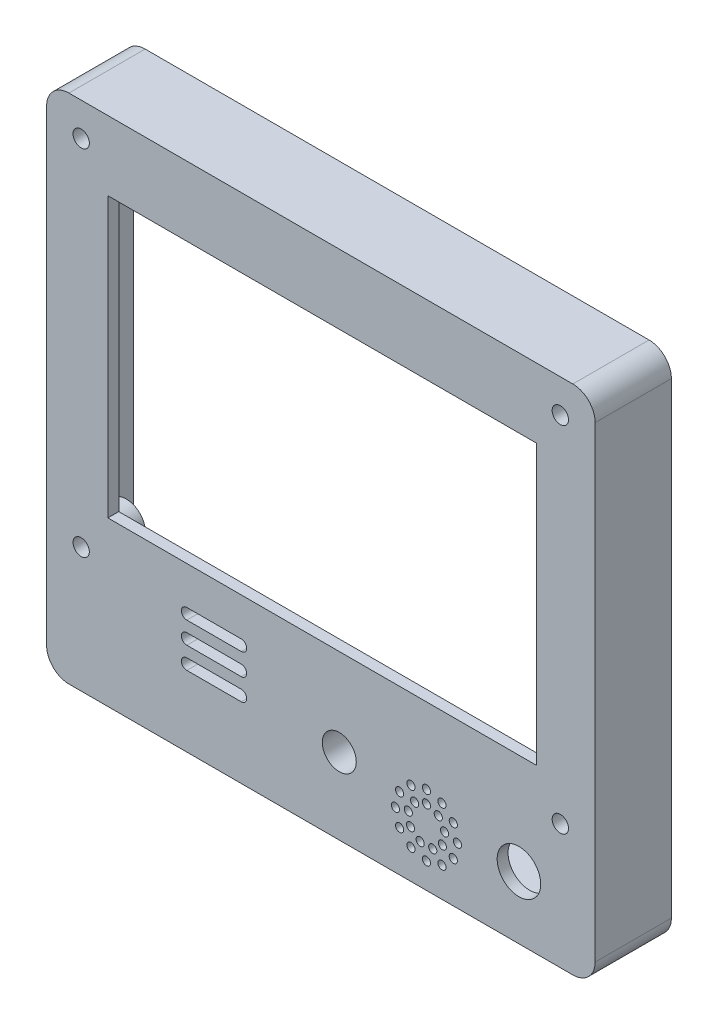
SolidWorks part; units mm, degrees
ref_plane "Front Plane" through (0, 0, 0) normal (0, 0, 1) x (1, 0, 0)
ref_plane "Top Plane" through (0, 0, 0) normal (0, 1, 0) x (1, 0, 0)
ref_plane "Right Plane" through (0, 0, 0) normal (1, 0, 0) x (0, 0, -1)
sketch "Sketch1" plane through (0, 0, 0) normal (0, 0, 1) x (1, 0, 0)
  line L1 (-50.375, -47) -> (50.375, -47)
  line L2 (-50.375, -47) -> (-50.375, 47)
  line L3 (-50.375, 47) -> (50.375, 47)
  line L4 (50.375, -47) -> (50.375, 47)
  line L5 (-50.375, -47) -> (50.375, 47) construction
  line L6 (-50.375, 47) -> (50.375, -47) construction
  point P0 (0, 0)
  dimension "D1" = 100.75
  dimension "D2" = 94
extrude "Boss-Extrude1" add sketch "Sketch1" along normal blind 14
shell "Shell1" thickness 2 removed face at (0, 0, 0)
sketch "Sketch2" plane through (0, 0, 12) normal (0, 0, -1) x (-1, 0, 0)
  line L0 (-43.975, 40.9) -> (44.025, 40.9) construction
  line L1 (44.025, 40.9) -> (44.025, -24.1) construction
  line L2 (44.025, -24.1) -> (-43.975, -24.1) construction
  line L3 (-43.975, -24.1) -> (-43.975, 40.9) construction
  line L4 (-48.375, 45) -> (48.375, 45) construction
  line L5 (-48.375, -45) -> (-48.375, 45) construction
  line L8 (48.375, -45) -> (-48.375, -45) construction
  line L9 (-50.375, -47) -> (-50.375, 47) construction
  circle A0 centre (-43.975, 40.9) radius 3.5
  circle A1 centre (-43.975, -24.1) radius 3.5
  circle A2 centre (44.025, 40.9) radius 3.5
  circle A3 centre (44.025, -24.1) radius 3.5
  circle A4 centre (-3.375, -33) radius 4
  dimension "D1" = 8
  dimension "D2" = 7
  dimension "D5" = 7
  dimension "D3" = 88
  dimension "D4" = 65
  dimension "D6" = 4.1
  dimension "D7" = 4.4
  dimension "D8" = 12
  dimension "D9" = 47
extrude "Boss-Extrude2" add sketch "Sketch2" along normal blind 6.3
sketch "Sketch3" plane through (0, 0, 14) normal (0, 0, 1) x (1, 0, 0)
  line L0 (-50.375, 47) -> (-50.375, -47) construction
  line L1 (-39.125, -17) -> (39.625, -17)
  line L2 (-39.125, -17) -> (-39.125, 34.25)
  line L3 (-39.125, 34.25) -> (39.625, 34.25)
  line L4 (39.625, -17) -> (39.625, 34.25)
  line L5 (-39.125, -17) -> (39.625, 34.25) construction
  line L6 (-39.125, 34.25) -> (39.625, -17) construction
  line L7 (50.375, 47) -> (-50.375, 47) construction
  line L8 (-44.025, 40.9) -> (43.975, 40.9) construction
  line L9 (43.975, 40.9) -> (43.975, -24.1) construction
  line L10 (-44.025, 40.9) -> (-44.025, -24.1) construction
  line L11 (-44.025, -24.1) -> (43.975, -24.1) construction
  line L12 (-24.625, -25) -> (-14.625, -25) construction
  line L13 (-24.625, -24) -> (-14.625, -24)
  line L14 (-24.625, -26) -> (-14.625, -26)
  line L15 (-24.625, -29) -> (-14.625, -29) construction
  line L16 (-24.625, -28) -> (-14.625, -28)
  line L17 (-24.625, -30) -> (-14.625, -30)
  line L18 (-24.625, -33) -> (-14.625, -33) construction
  line L19 (-24.625, -32) -> (-14.625, -32)
  line L20 (-24.625, -34) -> (-14.625, -34)
  line L21 (-50.375, -47) -> (50.375, -47) construction
  line L22 (-24.625, -33) -> (-24.625, -25) construction
  line L23 (50.375, -47) -> (50.375, 47) construction
  line L24 (50.375, -47) -> (50.375, 47) construction
  circle A0 centre (-44.025, 40.9) radius 1.5
  circle A1 centre (43.975, 40.9) radius 1.5
  circle A2 centre (43.975, -24.1) radius 1.5
  circle A3 centre (-44.025, -24.1) radius 1.5
  arc A5 (-24.625, -24) -> (-24.625, -26) centre (-24.625, -25) ccw
  arc A6 (-14.625, -26) -> (-14.625, -24) centre (-14.625, -25) ccw
  arc A7 (-24.625, -28) -> (-24.625, -30) centre (-24.625, -29) ccw
  arc A8 (-14.625, -30) -> (-14.625, -28) centre (-14.625, -29) ccw
  arc A9 (-24.625, -32) -> (-24.625, -34) centre (-24.625, -33) ccw
  arc A10 (-14.625, -34) -> (-14.625, -32) centre (-14.625, -33) ccw
  circle A11 centre (36.375, -35.5) radius 4
  circle A12 centre (3.375, -33) radius 3.125
  circle A13 centre (19.3883, -36.6212) radius 3.3782 construction
  circle A14 centre (19.3883, -33.243) radius 0.75
  circle A15 centre (19.3883, -36.6212) radius 3.3782 construction
  circle A16 centre (21.5598, -34.0333) radius 0.75
  circle A17 centre (19.3883, -36.6212) radius 3.3782 construction
  circle A18 centre (22.7152, -36.0346) radius 0.75
  circle A19 centre (19.3883, -36.6212) radius 3.3782 construction
  circle A20 centre (22.3139, -38.3103) radius 0.75
  circle A21 centre (19.3883, -36.6212) radius 3.3782 construction
  circle A22 centre (20.5437, -39.7957) radius 0.75
  circle A23 centre (19.3883, -36.6212) radius 3.3782 construction
  circle A24 centre (18.2328, -39.7957) radius 0.75
  circle A25 centre (19.3883, -36.6212) radius 3.3782 construction
  circle A26 centre (16.4626, -38.3103) radius 0.75
  circle A27 centre (19.3883, -36.6212) radius 3.3782 construction
  circle A28 centre (16.0614, -36.0346) radius 0.75
  circle A29 centre (19.3883, -36.6212) radius 3.3782 construction
  circle A30 centre (17.2168, -34.0333) radius 0.75
  circle A31 centre (19.3883, -36.6212) radius 5.6942 construction
  circle A32 centre (19.3883, -30.927) radius 0.75
  circle A33 centre (22.2354, -31.6899) radius 0.75
  circle A34 centre (24.3196, -33.7741) radius 0.75
  circle A35 centre (25.0825, -36.6212) radius 0.75
  circle A36 centre (24.3196, -39.4683) radius 0.75
  circle A37 centre (22.2354, -41.5525) radius 0.75
  circle A38 centre (19.3883, -42.3154) radius 0.75
  circle A39 centre (16.5412, -41.5525) radius 0.75
  circle A40 centre (14.4569, -39.4683) radius 0.75
  circle A41 centre (13.6941, -36.6212) radius 0.75
  circle A42 centre (14.4569, -33.7741) radius 0.75
  circle A43 centre (16.5412, -31.6899) radius 0.75
  point P0 (0.25, 8.625)
  point P17 (-19.625, -25)
  point P26 (-19.625, -29)
  point P33 (-19.625, -33)
  point P79 (19.3883, -36.6212)
  point P105 (19.3883, -36.6212)
  dimension "D21" = 8
  dimension "D24" = 6.25
  dimension "D25" = 1.5
  dimension "D27" = 1.5
  dimension "D29" = 3
  dimension "D1" = 78.75
  dimension "D2" = 51.25
  dimension "D3" = 11.25
  dimension "D4" = 12.75
  dimension "D5" = 6.4
  dimension "D6" = 6.1
  dimension "D7" = 88
  dimension "D8" = 65
  dimension "D9" = 2
  dimension "D10" = 2
  dimension "D11" = 2
  dimension "D12" = 10
  dimension "D13" = 10
  dimension "D14" = 10
  dimension "D15" = 4
  dimension "D16" = 4
  dimension "D17" = 14
  dimension "D18" = 25.75
  dimension "D19" = 14
  dimension "D20" = 11.5
  dimension "D22" = 14
  dimension "D23" = 47
  dimension "D26" = 9
  dimension "D28" = 12
extrude "Cut-Extrude1" cut sketch "Sketch3" against normal through all
fillet "Fillet1" radius 4.1 4 edges at (-50.375, -47, 7) (-50.375, 47, 7) (50.375, 47, 7) (50.375, -47, 7)
